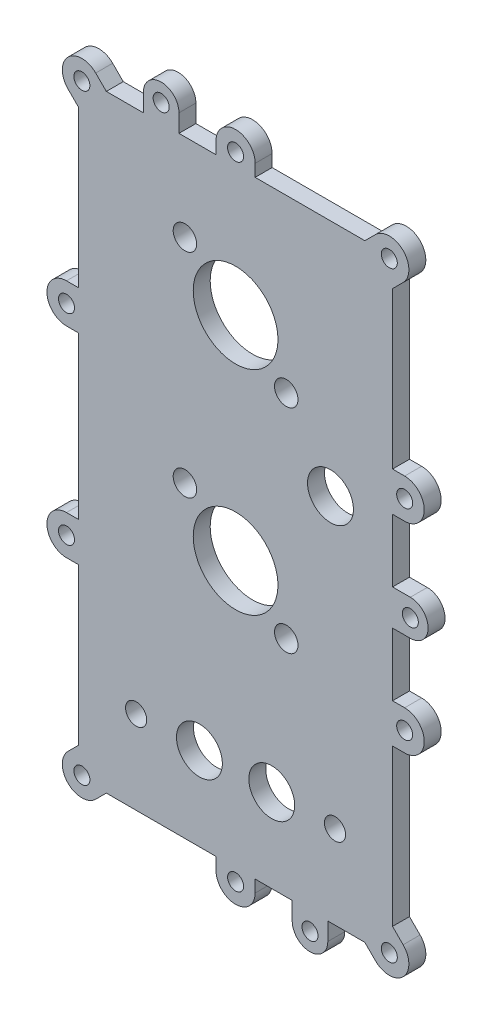
SolidWorks part; units mm, degrees
material "Acrylic (Medium-high impact)"
ref_plane "X-Y Datum" through (0, 0, 0) normal (0, 0, 1) x (1, 0, 0)
ref_plane "X-Z Datum" through (0, 0, 0) normal (0, 1, 0) x (1, 0, 0)
ref_plane "Y-Z Datum" through (0, 0, 0) normal (1, 0, 0) x (0, 0, -1)
sketch "Sketch1" plane through (0, 0, 0) normal (0, 0, 1) x (1, 0, 0)
  line L60 (50.35, 7.779) -> (19.5282, 7.779)
  line L61 (50.35, 11.1887) -> (50.35, 7.779)
  line L62 (61.35, 7.779) -> (61.35, 11.1887)
  line L63 (92.1718, 7.779) -> (61.35, 7.779)
  line L64 (95.1523, 10.7595) -> (92.1718, 7.779)
  line L65 (99.95, 0.0008) -> (102.9304, 2.9813)
  line L66 (99.95, -43.902) -> (99.95, 0.0008)
  line L67 (103.3597, -43.902) -> (99.95, -43.902)
  line L68 (99.95, -54.902) -> (103.3597, -54.902)
  line L69 (99.95, -100.29) -> (99.95, -54.902)
  line L70 (103.3597, -100.29) -> (99.95, -100.29)
  line L71 (99.95, -111.29) -> (103.3597, -111.29)
  line L72 (99.95, -155.1928) -> (99.95, -111.29)
  line L73 (102.9304, -158.1733) -> (99.95, -155.1928)
  line L74 (92.1718, -162.971) -> (95.1523, -165.9514)
  line L75 (61.35, -162.971) -> (92.1718, -162.971)
  line L76 (61.35, -166.3807) -> (61.35, -162.971)
  line L77 (50.35, -162.971) -> (50.35, -166.3807)
  line L78 (19.5282, -162.971) -> (50.35, -162.971)
  line L79 (16.5477, -165.9514) -> (19.5282, -162.971)
  line L80 (11.75, -155.1928) -> (8.7695, -158.1733)
  line L81 (11.75, -111.29) -> (11.75, -155.1928)
  line L82 (8.3403, -111.29) -> (11.75, -111.29)
  line L83 (11.75, -100.29) -> (8.3403, -100.29)
  line L84 (11.75, -54.902) -> (11.75, -100.29)
  line L85 (8.3403, -54.902) -> (11.75, -54.902)
  line L86 (11.75, -43.902) -> (8.3403, -43.902)
  line L87 (11.75, 0.0008) -> (11.75, -43.902)
  line L88 (8.7695, 2.9813) -> (11.75, 0.0008)
  line L89 (19.5282, 7.779) -> (16.5477, 10.7595)
  arc A20 (61.35, 11.1887) -> (50.35, 11.1887) centre (55.85, 11.1887) ccw
  arc A21 (102.9304, 2.9813) -> (95.1523, 10.7595) centre (99.0413, 6.8704) ccw
  arc A22 (103.3597, -54.902) -> (103.3597, -43.902) centre (103.3597, -49.402) ccw
  arc A23 (103.3597, -111.29) -> (103.3597, -100.29) centre (103.3597, -105.79) ccw
  arc A24 (95.1523, -165.9514) -> (102.9304, -158.1733) centre (99.0413, -162.0624) ccw
  arc A25 (50.35, -166.3807) -> (61.35, -166.3807) centre (55.85, -166.3807) ccw
  arc A26 (8.7695, -158.1733) -> (16.5477, -165.9514) centre (12.6586, -162.0624) ccw
  arc A27 (8.3403, -100.29) -> (8.3403, -111.29) centre (8.3403, -105.79) ccw
  arc A28 (8.3403, -43.902) -> (8.3403, -54.902) centre (8.3403, -49.402) ccw
  arc A29 (16.5477, 10.7595) -> (8.7695, 2.9813) centre (12.6586, 6.8704) ccw
extrude "Boss-Extrude1" add sketch "Sketch1" against normal blind 4.7625
hole_wizard "M4 Clearance Hole1" positions "Sketch2" profile "Sketch3" hole size "M4" standard "ANSI Metric" end condition through all
sketch "Sketch2" plane through (0, 0, -4.7625) normal (0, 0, -1) x (-1, 0, 0)
  point P0 (-12.6586, -162.0624)
  point P2 (-55.85, -166.3807)
  point P4 (-99.0413, -162.0624)
  point P6 (-103.3597, -105.79)
  point P8 (-103.3597, -49.402)
  point P10 (-99.0413, 6.8704)
  point P14 (-12.6586, 6.8704)
  point P16 (-8.3403, -49.402)
  point P18 (-8.3403, -105.79)
  point P22 (-55.85, 11.1887)
sketch "Sketch3" plane through (12.6586, -162.0624, -4.7625) normal (1, 0, 0) x (0, 1, 0)
  line L0 (0, 0) -> (0, 4.7625)
  line L1 (0, 4.7625) -> (2.25, 4.7625)
  line L2 (2.25, 4.7625) -> (2.25, 0)
  line L5 (2.25, 0) -> (0, 0)
  line L11 (0, -6.35) -> (0, 107.95) construction
  dimension "Thru Hole Dia." = 4.5
  dimension "Thru Hole Depth" = 4.7625
sketch "Sketch4" plane through (0, 0, -4.7625) normal (0, 0, -1) x (-1, 0, 0)
  line L8 (-93.95, -3.555) -> (-93.95, -119.546)
  line L9 (-93.95, -119.546) -> (-17.75, -119.546)
  line L10 (-17.75, -119.546) -> (-17.75, -3.555)
  line L11 (-23.084, 1.779) -> (-88.616, 1.779)
  line L16 (-95.5403, -3.555) -> (-95.5403, -151.637)
  line L17 (-88.616, -158.5613) -> (-23.084, -158.5613)
  line L18 (-16.1597, -151.637) -> (-16.1597, -3.555)
  line L19 (-23.084, 3.3693) -> (-88.616, 3.3693)
  line L24 (-93.95, -122.046) -> (-93.95, -151.637)
  line L25 (-17.75, -122.046) -> (-93.95, -122.046)
  line L26 (-17.75, -151.637) -> (-17.75, -122.046)
  line L27 (-88.616, -156.971) -> (-23.084, -156.971)
  circle A0 centre (-41.6161, -16.6659) radius 3.3
  circle A1 centre (-70.0839, -40.3003) radius 3.3
  circle A2 centre (-27.91, -139.5085) radius 2.9766
  circle A3 centre (-41.6161, -76.4667) radius 3.3
  circle A4 centre (-83.79, -139.5085) radius 2.9766
  circle A5 centre (-70.0839, -100.1011) radius 3.3
  arc A8 (-17.75, -3.555) -> (-23.084, 1.779) centre (-23.084, -3.555) ccw
  arc A9 (-88.616, 1.779) -> (-93.95, -3.555) centre (-88.616, -3.555) ccw
  circle A14 centre (-66.01, -139.5085) radius 6.445
  arc A16 (-95.5403, -151.637) -> (-88.616, -158.5613) centre (-88.616, -151.637) ccw
  arc A17 (-23.084, -158.5613) -> (-16.1597, -151.637) centre (-23.084, -151.637) ccw
  arc A18 (-16.1597, -3.555) -> (-23.084, 3.3693) centre (-23.084, -3.555) ccw
  arc A19 (-88.616, 3.3693) -> (-95.5403, -3.555) centre (-88.616, -3.555) ccw
  arc A22 (-23.084, -156.971) -> (-17.75, -151.637) centre (-23.084, -151.637) ccw
  arc A23 (-93.95, -151.637) -> (-88.616, -156.971) centre (-88.616, -151.637) ccw
  circle A32 centre (-82.52, -59.221) radius 6.445
  circle A34 centre (-45.69, -139.5085) radius 6.445
  circle A36 centre (-55.85, -88.2839) radius 11.9
  circle A38 centre (-55.85, -28.4831) radius 11.9
  dimension "D1" = 6.6
  dimension "D2" = 12.89
  dimension "D3" = 5.9531
  dimension "D4" = 23.8
extrude "Cut-Extrude1" cut sketch "Sketch4" against normal blind 4.7625 contours A38 | A32 | A36 | A2 | A34 | A14 | A4 | A0 | A1 | A3 | A5 region at (41.6161, -16.6659, -4.7625) region at (70.0839, -40.3003, -4.7625) region at (27.91, -139.5085, -4.7625) region at (41.6161, -76.4667, -4.7625) region at (83.79, -139.5085, -4.7625) region at (70.0839, -100.1011, -4.7625) region at (66.01, -139.5085, -4.7625) region at (82.52, -59.221, -4.7625) region at (45.69, -139.5085, -4.7625) region at (55.85, -88.2839, -4.7625) region at (55.85, -28.4831, -4.7625)
sketch "Sketch5" plane through (0, 0, -6.35) normal (0, 0, -1) x (-1, 0, 0)
  line L0 (-99.95, -77.596) -> (-104.95, -77.596) construction
  line L1 (-99.95, -100.29) -> (-99.95, -54.902) construction
  line L2 (-34.9391, 7.779) -> (-34.9391, 12.779) construction
  line L3 (-50.35, 7.779) -> (-19.5282, 7.779) construction
  line L4 (-76.7609, -162.971) -> (-76.7609, -167.971) construction
  line L6 (-61.35, -162.971) -> (-92.1718, -162.971) construction
  line L7 (-104.95, -72.596) -> (-99.95, -72.596)
  line L8 (-104.95, -82.596) -> (-99.95, -82.596)
  line L9 (-81.7609, -167.971) -> (-81.7609, -162.971)
  line L10 (-71.7609, -167.971) -> (-71.7609, -162.971)
  line L11 (-29.9391, 12.779) -> (-29.9391, 7.779)
  line L12 (-39.9391, 12.779) -> (-39.9391, 7.779)
  line L13 (-81.7609, -162.971) -> (-71.7609, -162.971)
  line L14 (-99.95, -82.596) -> (-99.95, -72.596)
  line L15 (-39.9391, 7.779) -> (-29.9391, 7.779)
  circle A1 centre (-103.3597, -105.79) radius 2.25
  circle A2 centre (-104.95, -77.596) radius 2.25 construction
  circle A3 centre (-34.9391, 12.779) radius 2.25 construction
  circle A4 centre (-76.7609, -167.971) radius 2.25 construction
  circle A5 centre (-104.95, -77.596) radius 4 construction
  circle A6 centre (-104.95, -77.596) radius 5
  circle A7 centre (-76.7609, -167.971) radius 5
  circle A8 centre (-34.9391, 12.779) radius 5
  dimension "D1" = 4.5
  dimension "D2" = 4.5
  dimension "D4" = 8
  dimension "D5" = 10
  dimension "D3" = 5
sketch "Sketch6" plane through (0, 0, 0) normal (0, 0, 1) x (1, 0, 0)
  line L0 (39.9391, 12.779) -> (39.9391, 7.779) construction
  line L1 (39.9391, 7.779) -> (29.9391, 7.779) construction
  line L2 (29.9391, 12.779) -> (29.9391, 7.779) construction
  line L3 (81.7609, -167.971) -> (81.7609, -162.971) construction
  line L4 (81.7609, -162.971) -> (71.7609, -162.971) construction
  line L5 (71.7609, -167.971) -> (71.7609, -162.971) construction
  line L6 (104.95, -72.596) -> (99.95, -72.596) construction
  line L7 (99.95, -82.596) -> (99.95, -72.596) construction
  line L8 (104.95, -82.596) -> (99.95, -82.596) construction
  line L9 (39.9391, 12.779) -> (39.9391, 7.779)
  line L10 (39.9391, 7.779) -> (29.9391, 7.779)
  line L11 (29.9391, 12.779) -> (29.9391, 7.779)
  line L12 (81.7609, -167.971) -> (81.7609, -162.971)
  line L13 (81.7609, -162.971) -> (71.7609, -162.971)
  line L14 (71.7609, -167.971) -> (71.7609, -162.971)
  line L15 (104.95, -72.596) -> (99.95, -72.596)
  line L16 (99.95, -82.596) -> (99.95, -72.596)
  line L17 (104.95, -82.596) -> (99.95, -82.596)
  circle A1 centre (103.3597, -105.79) radius 2.25
  circle A2 centre (103.3597, -105.79) radius 2.25
  circle A3 centre (34.9391, 12.779) radius 5
  circle A4 centre (34.9391, 12.779) radius 5
  circle A5 centre (76.7609, -167.971) radius 5
  circle A6 centre (76.7609, -167.971) radius 5
  circle A7 centre (104.95, -77.596) radius 5
  circle A8 centre (104.95, -77.596) radius 5
  dimension "D1" = 0
  dimension "D2" = 0
  dimension "D3" = 0
  dimension "D4" = 0
extrude "Boss-Extrude3" add sketch "Sketch6" against normal blind 4.7625 contours A6 L12 L13 L14 | A8 L15 L16 L17 | A8 | A4 L11 L10 L9 | A4 | A8 L16 L17 | A4 L10 L9 | A6 L13 L14 | A6 region at (34.9391, 12.779, 0) region at (38.8222, 8.8959, 0) region at (31.0559, 8.8959, 0) region at (80.644, -164.0878, 0) region at (72.8777, -164.0878, 0) region at (101.0668, -73.7128, 0) region at (104.95, -77.596, 0) region at (101.0668, -81.4791, 0)
hole_wizard "M4 Clearance Hole2" positions "Sketch8" profile "Sketch9" hole size "M4" standard "ANSI Metric" end condition through all
sketch "Sketch8" plane through (0, 0, 0) normal (0, 0, 1) x (1, 0, 0)
  point P11 (34.9391, 12.779)
  point P13 (104.95, -77.596)
  point P15 (76.7609, -167.971)
sketch "Sketch9" plane through (34.9391, 12.779, 0) normal (1, 0, 0) x (0, -1, 0)
  line L0 (0, 0) -> (0, 4.7625)
  line L1 (0, 4.7625) -> (2.25, 4.7625)
  line L2 (2.25, 4.7625) -> (2.25, 0)
  line L5 (2.25, 0) -> (0, 0)
  line L11 (0, -6.35) -> (0, 107.95) construction
  dimension "Thru Hole Dia." = 4.5
  dimension "Thru Hole Depth" = 4.7625
